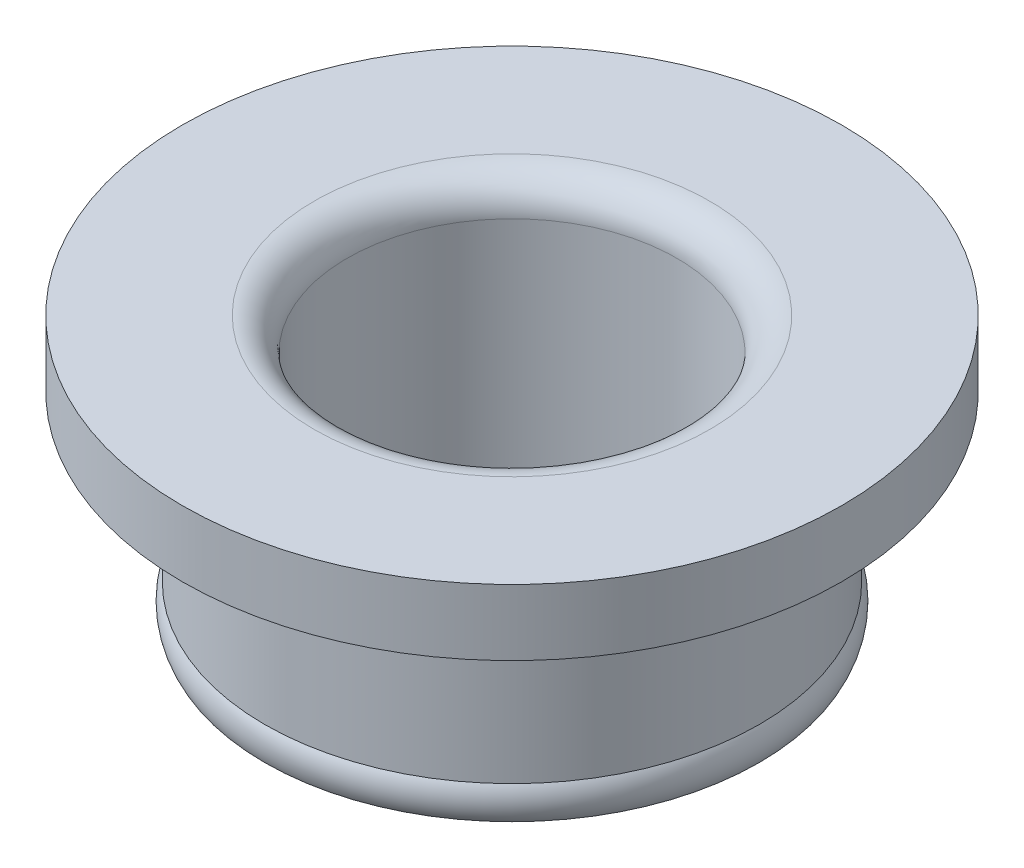
SolidWorks part; units mm, degrees
ref_plane "Front Plane" through (0, 0, 0) normal (0, 0, 1) x (1, 0, 0)
ref_plane "Top Plane" through (0, 0, 0) normal (0, 1, 0) x (1, 0, 0)
ref_plane "Right Plane" through (0, 0, 0) normal (1, 0, 0) x (0, 0, -1)
sketch "Sketch1" plane through (0, 0, 0) normal (0, 1, 0) x (1, 0, 0)
  circle A0 centre (0, 0) radius 6.35
  circle A1 centre (0, 0) radius 12.7
  circle A2 centre (0, 0) radius 9.525
  dimension "D1" = 12.7
  dimension "D2" = 25.4
  dimension "D3" = 19.05
extrude "Boss-Extrude1" add sketch "Sketch1" along normal blind 2.54 contours A0 | A1 region at (0, 0, 0)
extrude "Boss-Extrude2" add sketch "Sketch1<3>" against normal blind 7.62 contours A2 A0 region at (-9.2556, 0, 0)
sketch "Sketch1<3>" plane through (0, 0, 0) normal (0, 1, 0) x (1, 0, 0) same geometry as "Sketch1"
fillet "Fillet1" radius 1.27 1 edges at (0, 2.54, 6.35)
fillet "Fillet2" radius 0.762 1 edges at (0, 0, 9.525)
sketch "Sketch2" plane through (0, 0, 0) normal (1, 0, 0) x (0, 0, -1)
  line L0 (9.525, -7.62) -> (9.525, -0.762) construction
  line L1 (9.525, -6.35) -> (9.525, -7.62)
  arc A0 (9.525, -7.62) -> (9.525, -6.35) centre (8.4251, -6.985) ccw
  dimension "D1" = 1.27
  dimension "D2" = 1.27
ref_axis "Axis1" through (0, 3.048, 0) along (0, -1, 0)
revolve "Revolve1" add sketch "Sketch2" angle 360 about axis through (0, 3.048, 0) along (0, -1, 0)
